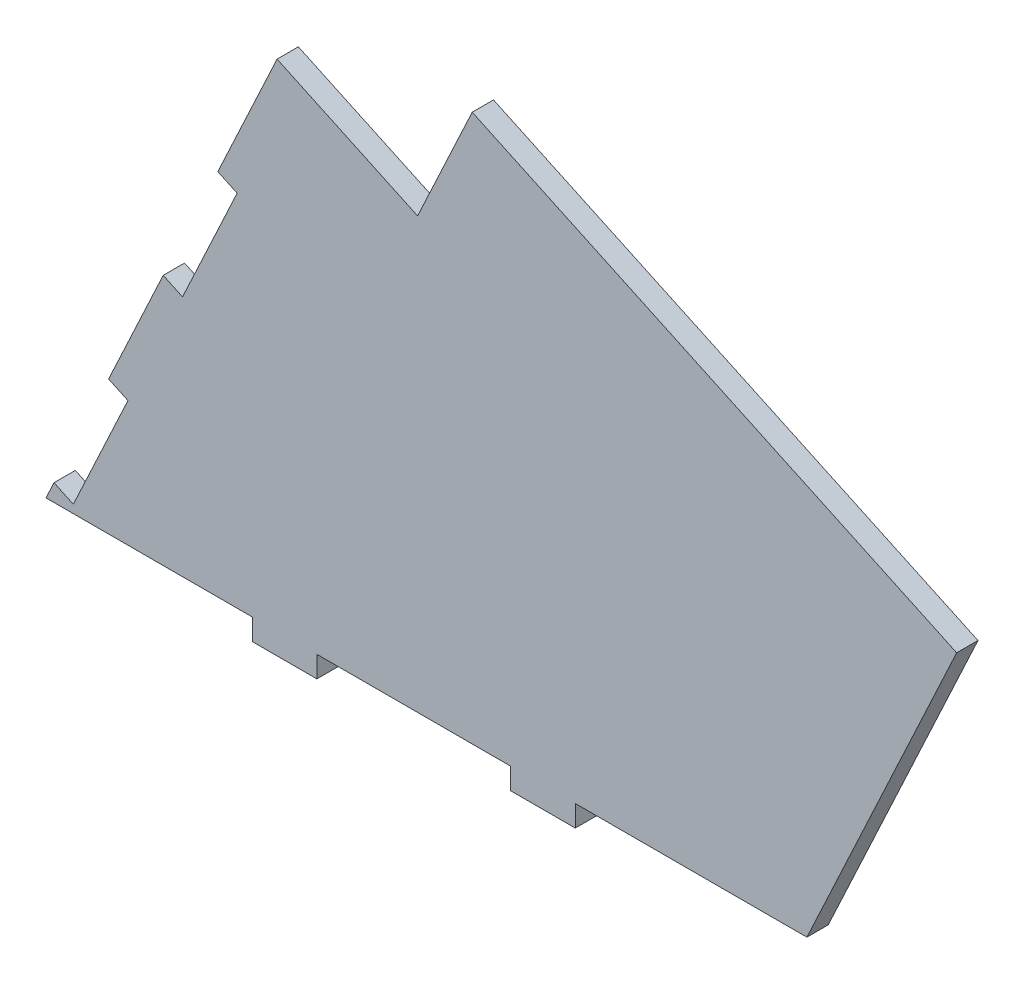
SolidWorks part; units mm, degrees
material "Balsa"
ref_plane "Front Plane" through (0, 0, 0) normal (0, 0, 1) x (1, 0, 0)
ref_plane "Top Plane" through (0, 0, 0) normal (0, 1, 0) x (1, 0, 0)
ref_plane "Right Plane" through (0, 0, 0) normal (1, 0, 0) x (0, 0, -1)
sketch "Sketch1" plane through (0, 0, 396.7) normal (0, 0, 1) x (1, 0, 0)
  line L0 (-321.5462, 12.6346) -> (-203.7639, 12.6346)
  line L1 (-250.629, 107.9281) -> (-255.5737, 97.3243) construction
  line L2 (-321.5462, 12.6346) -> (-285.7774, 89.341)
  line L3 (-285.7774, 89.341) -> (-264.026, 79.1982)
  line L4 (-264.026, 79.1982) -> (-255.5737, 97.3243)
  line L5 (-255.5737, 97.3243) -> (-180.5794, 62.354)
  line L6 (-180.5794, 62.354) -> (-203.7639, 12.6346)
  line L7 (-176.6689, 0) -> (-153.4844, 49.7193) construction
  line L8 (-255.5737, 97.3243) -> (63.4467, -51.4373) construction
  line L10 (-327.4362, 0.0035) -> (-285.7774, 89.341) construction
  line L11 (-285.7774, 89.341) -> (-267.6513, 80.8887) construction
  dimension "D1" = 0
extrude "Boss-Extrude1" add sketch "Sketch1" against normal blind 3.3
sketch "Sketch2" plane through (0, 0, 396.7) normal (0, 0, 1) x (1, 0, 0)
  line L0 (-311.8564, 33.4145) -> (-320.3088, 15.2883)
  line L1 (-311.8564, 33.4145) -> (-308.8656, 32.0199)
  line L2 (-320.3088, 15.2883) -> (-317.3179, 13.8937)
  line L3 (-308.8656, 32.0199) -> (-317.3179, 13.8937)
  line L4 (-303.404, 51.5407) -> (-294.9517, 69.6668)
  line L5 (-303.404, 51.5407) -> (-300.4132, 50.146)
  line L6 (-294.9517, 69.6668) -> (-291.9609, 68.2722)
  line L7 (-300.4132, 50.146) -> (-291.9609, 68.2722)
  line L8 (-300.4132, 50.146) -> (-291.9609, 68.2722) construction
  line L9 (-303.404, 51.5407) -> (-294.9517, 69.6668) construction
extrude "Cut-Extrude1" cut sketch "Sketch2" against normal blind 3.3
sketch "Sketch3" plane through (0, 0, 396.7) normal (0, 0, 1) x (1, 0, 0)
  line L0 (-239.6178, 9.3346) -> (-249.6178, 9.3346)
  line L1 (-239.6178, 9.3346) -> (-239.6178, 12.6346)
  line L2 (-249.6178, 9.3346) -> (-249.6178, 12.6346)
  line L3 (-239.6178, 12.6346) -> (-249.6178, 12.6346)
  line L4 (-279.6178, 9.3346) -> (-289.6178, 9.3346)
  line L5 (-279.6178, 9.3346) -> (-279.6178, 12.6346)
  line L6 (-289.6178, 9.3346) -> (-289.6178, 12.6346)
  line L7 (-279.6178, 12.6346) -> (-289.6178, 12.6346)
  line L8 (-321.5462, 12.6346) -> (-203.7639, 12.6346) construction
extrude "Boss-Extrude2" add sketch "Sketch3" against normal blind 3.3
